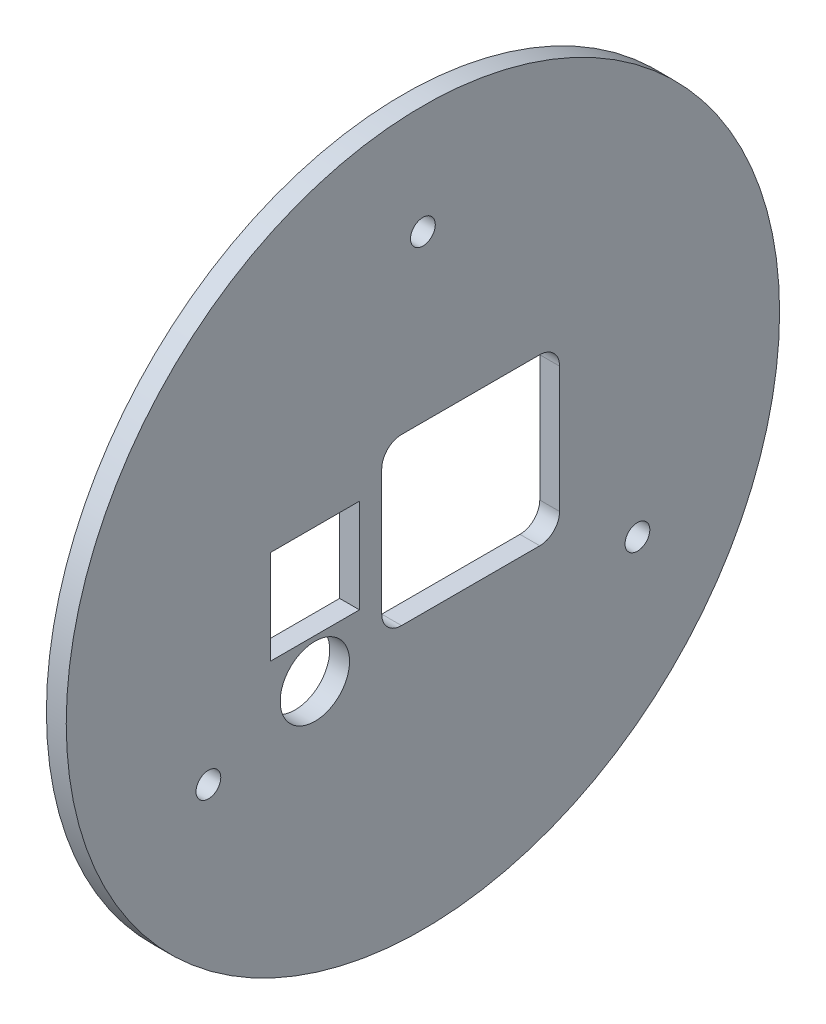
SolidWorks part; units mm, degrees
ref_plane "Front Plane" through (0, 0, 0) normal (0, 0, 1) x (1, 0, 0)
ref_plane "Top Plane" through (0, 0, 0) normal (0, 1, 0) x (1, 0, 0)
ref_plane "Right Plane" through (0, 0, 0) normal (1, 0, 0) x (0, 0, -1)
sketch "Sketch1" plane through (0, 0, 0) normal (1, 0, 0) x (0, 0, -1)
  line L0 (-72, 0) -> (72, 0) construction
  line L1 (-4.3098, 16.7) -> (23.5902, 16.7)
  line L2 (-8.3098, 12.7) -> (-8.3098, -12.7)
  line L3 (-4.3098, -16.7) -> (23.5902, -16.7)
  line L4 (27.5902, 12.7) -> (27.5902, -12.7)
  line L5 (69.7905, -17.7) -> (-69.7905, -17.7) construction
  line L6 (-21.8098, -17.7) -> (-21.8098, 68.6173) construction
  line L7 (-30.8098, 9.3) -> (-12.8098, 9.3)
  line L8 (-30.8098, 9.3) -> (-30.8098, -9.7)
  line L9 (-30.8098, -9.7) -> (-12.8098, -9.7)
  line L10 (-12.8098, 9.3) -> (-12.8098, -9.7)
  line L11 (0, 72) -> (0, -72) construction
  circle A0 centre (0, 0) radius 72
  circle A1 centre (-21.8098, -17.7) radius 7
  circle A2 centre (0, 50) radius 2.5
  circle A3 centre (43.3013, -25) radius 2.5
  circle A4 centre (-43.3013, -25) radius 2.5
  arc A5 (-4.3098, -16.7) -> (-8.3098, -12.7) centre (-4.3098, -12.7) cw
  arc A6 (23.5902, -16.7) -> (27.5902, -12.7) centre (23.5902, -12.7) ccw
  arc A7 (27.5902, 12.7) -> (23.5902, 16.7) centre (23.5902, 12.7) ccw
  arc A8 (-4.3098, 16.7) -> (-8.3098, 12.7) centre (-4.3098, 12.7) ccw
  point P13 (0, 0)
  point P29 (-8.3098, -16.7)
  point P32 (27.5902, -16.7)
  point P35 (27.5902, 16.7)
  point P38 (-8.3098, 16.7)
  point P39 (0, 0)
  dimension "D1" = 144
  dimension "D2" = 35.9
  dimension "D3" = 5
  dimension "D7" = 14
  dimension "D12" = 4
  dimension "D4" = 50
  dimension "D6" = 33.4
  dimension "D8" = 13.5
  dimension "D9" = 18
  dimension "D10" = 19
  dimension "D11" = 8
  dimension "D13" = 1
  dimension "D5" = 3
extrude "Boss-Extrude1" add sketch "Sketch1" along normal blind 4
